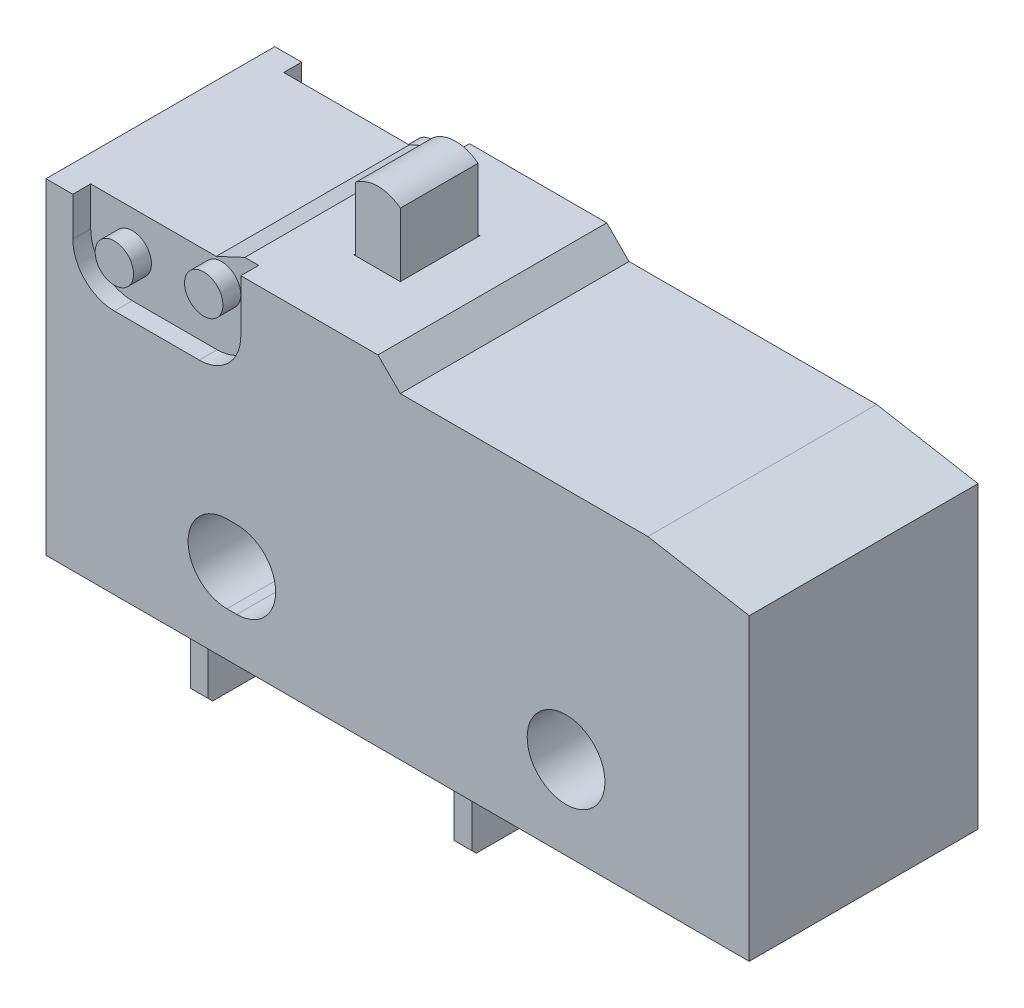
SolidWorks part; units mm, degrees
ref_plane "Front" through (0, 0, 0) normal (0, 0, 1) x (1, 0, 0)
ref_plane "Top" through (0, 0, 0) normal (0, 1, 0) x (1, 0, 0)
ref_plane "Right" through (0, 0, 0) normal (1, 0, 0) x (0, 0, -1)
sketch "Sketch2" plane through (0, 0, 0) normal (0, 0, 1) x (1, 0, 0)
  line L0 (-4.8514, 3.4671) -> (-4.572, 3.4671)
  line L1 (9.9949, 8.509) -> (7.1139, 9.017)
  line L2 (-9.9949, 9.271) -> (-9.9949, 0)
  line L3 (-9.9949, 0) -> (9.9949, 0)
  line L4 (9.9949, 8.509) -> (9.9949, 0)
  line L5 (-4.8514, 1.2573) -> (-4.572, 1.2573)
  line L6 (-4.7117, 3.4671) -> (-4.7117, 1.2573) construction
  line L7 (4.7879, 2.3622) -> (-4.572, 2.3622) construction
  line L8 (7.1139, 9.017) -> (0.0762, 9.017)
  line L9 (0.0762, 9.017) -> (-0.5588, 9.652)
  line L10 (-0.5588, 9.652) -> (-4.8514, 9.652)
  line L11 (-4.8514, 9.652) -> (-5.6646, 9.271)
  line L12 (-5.6646, 9.271) -> (-9.9949, 9.271)
  line L13 (-2.7051, 9.652) -> (-2.7051, 2.3622) construction
  line L14 (-4.8514, 9.652) -> (-4.8514, 3.4671) construction
  circle A0 centre (4.7879, 2.3622) radius 1.1049
  arc A1 (-4.8514, 3.4671) -> (-4.8514, 1.2573) centre (-4.8514, 2.3622) ccw
  arc A2 (-4.572, 1.2573) -> (-4.572, 3.4671) centre (-4.572, 2.3622) ccw
  dimension "D4" = 5.207
  dimension "D5" = 2.2098
  dimension "D6" = 2.4892
  dimension "D7" = 6.6548
  dimension "D8" = 7.2898
  dimension "D9" = 7.493
  dimension "D13" = 6.9088
  dimension "D1" = 19.9898
  dimension "D2" = 2.3622
  dimension "D3" = 9.4996
  dimension "D10" = 0.508
  dimension "D11" = 10
  dimension "D12" = 135
extrude "Extrude1" add sketch "Sketch2" along normal mid plane 6.5024
sketch "Sketch3" plane through (0, 0, 0) normal (0, 0, 1) x (1, 0, 0)
  line L0 (-3.3401, 9.271) -> (-3.3401, 11.4357)
  line L1 (-2.7051, 9.271) -> (-2.7051, 10.6426) construction
  line L2 (-2.0701, 11.4357) -> (-2.0701, 9.271)
  line L3 (-2.0701, 9.271) -> (-3.3401, 9.271)
  line L4 (-3.3401, 11.4357) -> (-2.0701, 11.4357) construction
  line L5 (-2.7051, 9.652) -> (-2.7051, 2.3622) construction
  line L6 (-5.6646, 9.271) -> (-9.9949, 9.271) construction
  arc A0 (-3.3401, 11.4357) -> (-2.0701, 11.4357) centre (-2.7051, 10.6426) cw
  arc A1 (-4.8514, 3.4671) -> (-4.8514, 1.2573) centre (-4.8514, 2.3622) ccw construction
  dimension "D1" = 9.2964
  dimension "D3" = 1.016
  dimension "D2" = 1.27
extrude "Extrude2" add sketch "Sketch3" along normal mid plane 2.2098 separate body
sketch "Sketch4" plane through (0, 9.652, 0) normal (0, 1, 0) x (-1, 0, 0)
  line L0 (2.0701, -1.1049) -> (3.3401, -1.1049) construction
  line L1 (3.3401, 1.1049) -> (3.3401, -1.1049) construction
  line L2 (2.0701, 1.1049) -> (2.0701, -1.1049) construction
  line L3 (3.3401, 1.1049) -> (2.0701, 1.1049) construction
  line L4 (2.0701, -1.1049) -> (3.3401, -1.1049) construction
  line L5 (3.3401, 1.1049) -> (3.3401, -1.1049) construction
  line L6 (2.0701, 1.1049) -> (2.0701, -1.1049) construction
  line L7 (3.3401, 1.1049) -> (2.0701, 1.1049) construction
  line L8 (3.3655, 1.1303) -> (3.3655, -1.1303)
  line L9 (2.0447, -1.1303) -> (3.3655, -1.1303)
  line L10 (2.0447, 1.1303) -> (2.0447, -1.1303)
  line L11 (3.3655, 1.1303) -> (2.0447, 1.1303)
  dimension "D1" = 0.0254
extrude "Cut-Extrude1" cut sketch "Sketch4" against normal blind 1.016
sketch "Sketch5" plane through (0, 0, 3.2512) normal (0, 0, 1) x (1, 0, 0)
  line L0 (-9.2329, 9.271) -> (-9.2329, 8.1661)
  line L1 (-8.0518, 6.985) -> (-5.6388, 6.985)
  line L2 (-4.4577, 8.1661) -> (-4.4577, 9.652)
  line L3 (-5.6646, 9.271) -> (-9.9949, 9.271) construction
  line L4 (-4.8514, 9.652) -> (-5.6646, 9.271) construction
  line L5 (-0.5588, 9.652) -> (-4.8514, 9.652) construction
  line L6 (-5.6646, 9.271) -> (-9.2329, 9.271)
  line L7 (-4.8514, 9.652) -> (-5.6646, 9.271)
  line L8 (-4.4577, 9.652) -> (-4.8514, 9.652)
  line L9 (-9.9949, 9.271) -> (-9.9949, 0) construction
  circle A0 centre (-5.5118, 8.6741) radius 0.5461
  circle A1 centre (-8.0518, 8.1661) radius 0.5461
  arc A2 (-9.2329, 8.1661) -> (-8.0518, 6.985) centre (-8.0518, 8.1661) ccw
  arc A3 (-5.6388, 6.985) -> (-4.4577, 8.1661) centre (-5.6388, 8.1661) ccw
  dimension "D4" = 0.0508
  dimension "D5" = 1.0922
  dimension "D6" = 2.54
  dimension "D7" = 0.508
  dimension "D1" = 0.762
  dimension "D2" = 0.508
  dimension "D3" = 0.635
extrude "Cut-Extrude2" cut sketch "Sketch5" against normal blind 0.508
mirror "Mirror1" about plane through (0, 0, 0) normal (0, 0, 1) of "Cut-Extrude2"
ref_plane "Plane1" through (-7.493, 0, 0) normal (1, 0, 0) x (0, 0, -1)
sketch "Sketch10" plane through (-7.493, 0, 0) normal (1, 0, 0) x (0, 0, -1)
  line L0 (-1.397, 0) -> (-1.397, -3.0734)
  line L1 (-1.27, -3.2004) -> (1.27, -3.2004)
  line L2 (1.397, -3.0734) -> (1.397, 0)
  line L3 (1.397, 0) -> (-1.397, 0)
  line L4 (0, -3.2004) -> (0, -1.7018) construction
  line L5 (0, 0) -> (0, -1.7018) construction
  line L6 (-1.397, -3.0734) -> (-1.27, -3.2004)
  line L7 (1.27, -3.2004) -> (1.397, -3.0734)
  circle A0 centre (0, -1.7018) radius 0.9017
  point P1 (-1.397, -3.2004)
  point P3 (1.397, -3.2004)
  dimension "D2" = 1.8034
  dimension "D1" = 3.2004
  dimension "D3" = 2.794
  dimension "D4" = 1.4986
  dimension "D5" = 0.127
  dimension "D6" = 45
  dimension "D7" = 0.127
  dimension "D8" = 45
extrude "Extrude6" add sketch "Sketch10" along normal mid plane 0.508
pattern_linear "LPattern1" count 2 spacing 7.493 along (1, 0, 0) of "Extrude6"
